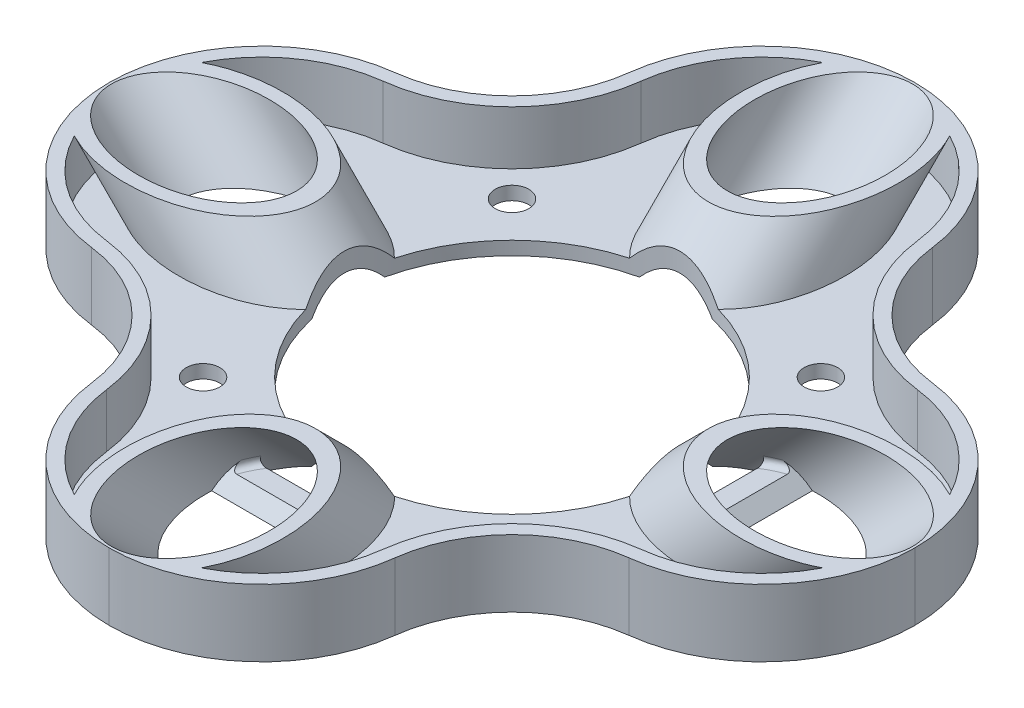
SolidWorks part; units mm, degrees
ref_plane "Front Plane" through (0, 0, 0) normal (0, 0, 1) x (1, 0, 0)
ref_plane "Top Plane" through (0, 0, 0) normal (0, 1, 0) x (1, 0, 0)
ref_plane "Right Plane" through (0, 0, 0) normal (1, 0, 0) x (0, 0, -1)
sketch "Sketch1" plane through (0, 0, 0) normal (0, 1, 0) x (1, 0, 0)
  line L0 (-55, 0) -> (55, 0) construction
  line L1 (0, -55) -> (0, 55) construction
  circle A0 centre (0, 0) radius 76.2 construction
  arc A1 (-28.6708, -50.8084) -> (-50.8142, -28.6647) centre (-53.8846, -53.8785) ccw
  arc A2 (-76.2, 0) -> (-50.8142, -28.6647) centre (-47.3235, 0) ccw
  arc A3 (-28.6708, -50.8084) -> (0, -76.2) centre (0, -47.3174) ccw
  arc A4 (-50.8084, 28.6708) -> (-28.6647, 50.8142) centre (-53.8785, 53.8846) ccw
  arc A5 (0, 76.2) -> (-28.6647, 50.8142) centre (0, 47.3235) ccw
  arc A6 (-50.8084, 28.6708) -> (-76.2, 0) centre (-47.3174, 0) ccw
  arc A8 (76.2, 0) -> (50.8142, 28.6647) centre (47.3235, 0) ccw
  arc A9 (28.6708, 50.8084) -> (0, 76.2) centre (0, 47.3174) ccw
  arc A10 (50.8084, -28.6708) -> (28.6647, -50.8142) centre (53.8785, -53.8846) ccw
  arc A11 (0, -76.2) -> (28.6647, -50.8142) centre (0, -47.3235) ccw
  arc A12 (50.8084, -28.6708) -> (76.2, 0) centre (47.3174, 0) ccw
  arc A13 (28.6708, 50.8084) -> (50.8142, 28.6647) centre (53.8846, 53.8785) ccw
  arc A14 (68.1558, 32.8668) -> (32.8772, 68.156) centre (53.8846, 53.8785) ccw [skipped]
  point P4 (0, 0)
  point P42 (0, 0)
  dimension "D1" = 152.4
  dimension "D2" = 50.8
  dimension "D3" = 53.8785
  dimension "D4" = 53.8846
  dimension "D5" = 4
extrude "Boss-Extrude1" add sketch "Sketch1" along normal blind 12.7
sketch "Sketch2" plane through (0, 0, 0) normal (0, -1, 0) x (1, 0, 0)
  line L0 (-63.5, 33.601) -> (-63.5, -33.601)
  line L1 (0, -55) -> (0, 55) construction
  dimension "D1" = 63.5
  dimension "D2" = 67.2021
sketch "Sketch5" plane through (0, 0, 0) normal (1, 0, 0) x (0, 0, -1)
  line L5 (0, 0) -> (0, -2.682) construction
  point P1 (8.9142, -8.0822)
  point P3 (1.73, -0.898)
  point P4 (0, 0)
ref_plane "Plane1" through (-31.75, 31.75, 0) normal (-0.7071, 0.7071, 0) x (0, 0, -1)
sketch "Sketch3" plane through (-31.75, 31.75, 0) normal (-0.7071, 0.7071, 0) x (0, 0, -1)
  line L0 (0, 55) -> (0, -55) construction
  line L1 (-33.601, 44.9013) -> (33.601, 44.9013) construction
  circle A0 centre (0, 32.2013) radius 12.3825
  point P2 (0, 4.1693)
  dimension "D1" = 24.765
  dimension "D2" = 12.7
extrude "Cut-Extrude1" cut sketch "Sketch3" against normal up to surface and the other way up to surface up to face at (0, 0, 0) other way up to face at (0, 12.7, 0)
ref_plane "Plane2" through (0, 0, 0) normal (0.7071, -0.7071, 0) x (-0.7071, -0.7071, 0)
pattern_circular "CirPattern2" count 4 over 360 about axis through (0, 0, 0) along (0, -1, 0) of "Cut-Extrude1" reverse direction yes
shell "Shell2" thickness 2.54 removed face at (75.751, 12.7, 0)
sketch "Sketch6" plane through (0, 0, 0) normal (0, -1, 0) x (1, 0, 0)
  circle A0 centre (0, 0) radius 31.75
  dimension "D1" = 63.5
sketch "Sketch8" plane through (0, 0, 0) normal (0, -1, 0) x (1, 0, 0)
  line L0 (-38.1, 38.1) -> (38.1, 38.1)
  line L1 (-44.45, -44.45) -> (44.45, -44.45)
  line L2 (-44.45, -44.45) -> (-44.45, 44.45)
  line L3 (-44.45, 44.45) -> (44.45, 44.45)
  line L4 (44.45, -44.45) -> (44.45, 44.45)
  line L5 (-44.45, -44.45) -> (44.45, 44.45) construction
  line L6 (-44.45, 44.45) -> (44.45, -44.45) construction
  line L7 (38.1, -38.1) -> (38.1, 38.1)
  line L8 (-38.1, -38.1) -> (38.1, -38.1)
  line L9 (-38.1, -38.1) -> (-38.1, 38.1)
  point P0 (0, 0)
  dimension "D1" = 6.35
  dimension "D2" = 88.9
extrude "Boss-Extrude5" add sketch "Sketch8" against normal blind 2.54
chamfer "Chamfer1" distance 2.54 angle 45 4 edges at (44.45, 2.54, 0) (-44.45, 2.54, 0) (0, 2.54, 44.45) (0, 2.54, -44.45)
extrude "Cut-Extrude2" cut sketch "Sketch6" against normal up to next contours A0
fillet "Fillet5" radius 1.016 8 edges at (-39.9434, 2.54, -10.9649) (-39.9434, 2.54, 10.9649) (39.9434, 2.54, 10.9649) (39.9434, 2.54, -10.9649) (-10.9649, 2.54, 39.9434) (10.9649, 2.54, 39.9434) (-10.9649, 2.54, -39.9434) (10.9649, 2.54, -39.9434)
sketch "Sketch11" plane through (0, 0, 0) normal (0, -1, 0) x (1, 0, 0)
  line L1 (-44.45, 12.3585) -> (-44.45, -12.3585) construction
  line L3 (12.3585, 44.45) -> (-12.3585, 44.45) construction
  circle A0 centre (-29.21, 29.21) radius 3.175
  dimension "D1" = 6.35
  dimension "D2" = 15.24
  dimension "D3" = 15.24
extrude "Cut-Extrude3" cut sketch "Sketch11" against normal up to next
pattern_circular "CirPattern3" count 4 over 360 about axis through (0, 0, 0) along (0, -1, 0) of "Cut-Extrude3"
sketch "Sketch12" plane through (0, 0, 0) normal (0, -1, 0) x (1, 0, 0)
  arc A0 (-50.8142, 28.6647) -> (-28.6708, 50.8084) centre (-53.8846, 53.8785) ccw construction
  arc A1 (-28.6647, -50.8142) -> (-50.8084, -28.6708) centre (-53.8785, -53.8846) ccw construction
  arc A2 (50.8142, -28.6647) -> (28.6708, -50.8084) centre (53.8846, -53.8785) ccw construction
  arc A3 (28.6647, 50.8142) -> (50.8084, 28.6708) centre (53.8785, 53.8846) ccw construction
  arc A4 (-50.8142, 28.6647) -> (-28.6708, 50.8084) centre (-53.8846, 53.8785) ccw
  arc A5 (-28.6647, -50.8142) -> (-50.8084, -28.6708) centre (-53.8785, -53.8846) ccw
  arc A6 (50.8142, -28.6647) -> (28.6708, -50.8084) centre (53.8846, -53.8785) ccw
  arc A7 (28.6647, 50.8142) -> (50.8084, 28.6708) centre (53.8785, 53.8846) ccw
  arc A8 (-50.8084, -28.6708) -> (-28.6647, -50.8142) centre (-36.8896, -36.8954) ccw
  arc A9 (-50.8142, 28.6647) -> (-28.6708, 50.8084) centre (-34.7582, 34.7524) cw
  arc A10 (28.6647, 50.8142) -> (50.8084, 28.6708) centre (32.9307, 32.9365) cw
  arc A11 (28.6708, -50.8084) -> (50.8142, -28.6647) centre (39.7425, -39.7366) ccw
extrude "Cut-Extrude4" cut sketch "Sketch12" against normal up to next
